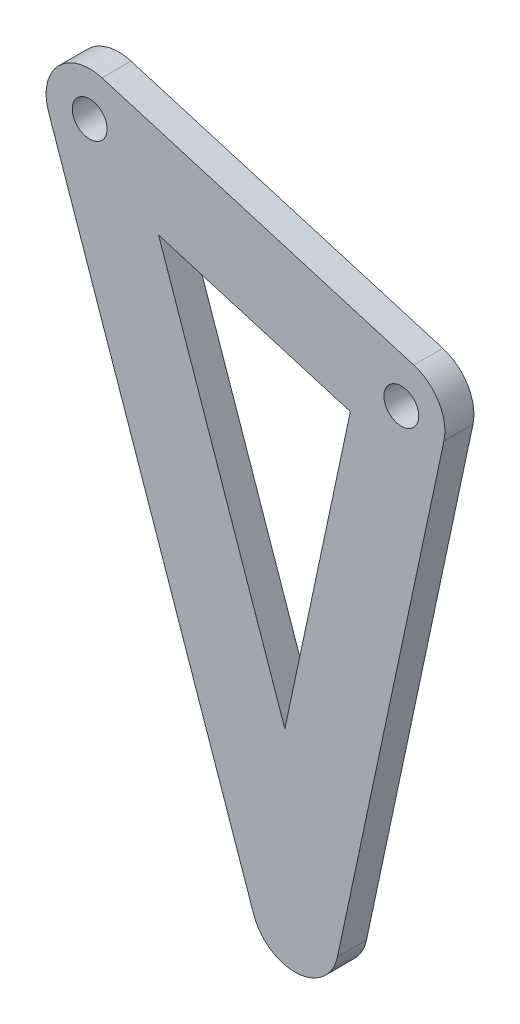
SolidWorks part; units mm, degrees
ref_plane "Plan de face" through (0, 0, 0) normal (0, 0, 1) x (1, 0, 0)
ref_plane "Plan de dessus" through (0, 0, 0) normal (0, 1, 0) x (1, 0, 0)
ref_plane "Plan de droite" through (0, 0, 0) normal (1, 0, 0) x (0, 0, -1)
sketch "Esquisse1" plane through (0, 0, 0) normal (0, 0, 1) x (1, 0, 0)
  line L0 (-138.3093, -40.0719) -> (-84.6394, -56.0578) construction
  line L1 (-136.1683, -32.884) -> (-82.4985, -48.8699)
  line L2 (-140.4503, -47.2599) -> (-86.7804, -63.2457)
  line L3 (-84.6394, -56.0578) -> (-102.9717, -142.1271) construction
  line L4 (-77.304, -57.6202) -> (-95.6363, -143.6895)
  line L5 (-91.9749, -54.4954) -> (-110.3072, -140.5647)
  line L6 (-102.9717, -142.1271) -> (-138.3093, -40.0719) construction
  line L7 (-110.0589, -144.5811) -> (-145.3965, -42.5259)
  line L8 (-95.8846, -139.6731) -> (-131.2221, -37.6179)
  line L9 (-126.4384, -51.4334) -> (-104.6967, -114.2236)
  line L10 (-104.6967, -114.2236) -> (-93.4176, -61.2688)
  line L11 (-93.4176, -61.2688) -> (-126.4384, -51.4334)
  line L12 (-77.304, -57.6202) -> (-95.6363, -143.6895)
  line L13 (-136.1683, -32.884) -> (-82.4985, -48.8699)
  line L14 (-145.3965, -42.5259) -> (-110.0589, -144.5811)
  arc A0 (-136.1683, -32.884) -> (-140.4503, -47.2599) centre (-138.3093, -40.0719) ccw
  arc A1 (-86.7804, -63.2457) -> (-82.4985, -48.8699) centre (-84.6394, -56.0578) ccw
  arc A2 (-77.304, -57.6202) -> (-91.9749, -54.4954) centre (-84.6394, -56.0578) ccw
  arc A3 (-110.3072, -140.5647) -> (-95.6363, -143.6895) centre (-102.9717, -142.1271) ccw
  arc A4 (-110.0589, -144.5811) -> (-95.8846, -139.6731) centre (-102.9717, -142.1271) ccw
  arc A5 (-131.2221, -37.6179) -> (-145.3965, -42.5259) centre (-138.3093, -40.0719) ccw
  point P4 (-111.4744, -48.0649)
  point P9 (-93.8056, -99.0924)
  point P18 (-120.6405, -91.0995)
  point P25 (-126.4384, -51.4334)
  point P26 (-104.6967, -114.2236)
  point P27 (-93.4176, -61.2688)
  dimension "D1" = 15
  dimension "D2" = 15
  dimension "D3" = 15
extrude "Boss.-Extru.1" add sketch "Esquisse1" against normal blind 5 contours A5 L8 L2 L5 A2 L1 | A1 A2 L5 L2 | L8 A5 A0 L2 | A3 L5 L8 L2 A0 L7 | A3 A4 L8 L5 | A4 L4 A1 L2 L5 L8 region at (-136.7804, -41.5352, 0) region at (-110.2437, -47.9543, 0) region at (-85.0141, -56.2802, 0) region at (-121.9561, -88.9548, 0) region at (-92.5435, -95.6921, 0) region at (-103.3244, -136.4223, 0)
sketch "Esquisse2" plane through (0, 0, 0) normal (0, 0, 1) x (1, 0, 0)
  circle A0 centre (-84.6394, -56.0578) radius 3
  circle A1 centre (-138.3093, -40.0719) radius 3
  dimension "D1" = 6
  dimension "D2" = 6
extrude "Enlèv. mat.-Extru.1" cut sketch "Esquisse2" against normal through all both and the other way through all contours A1 | A0
